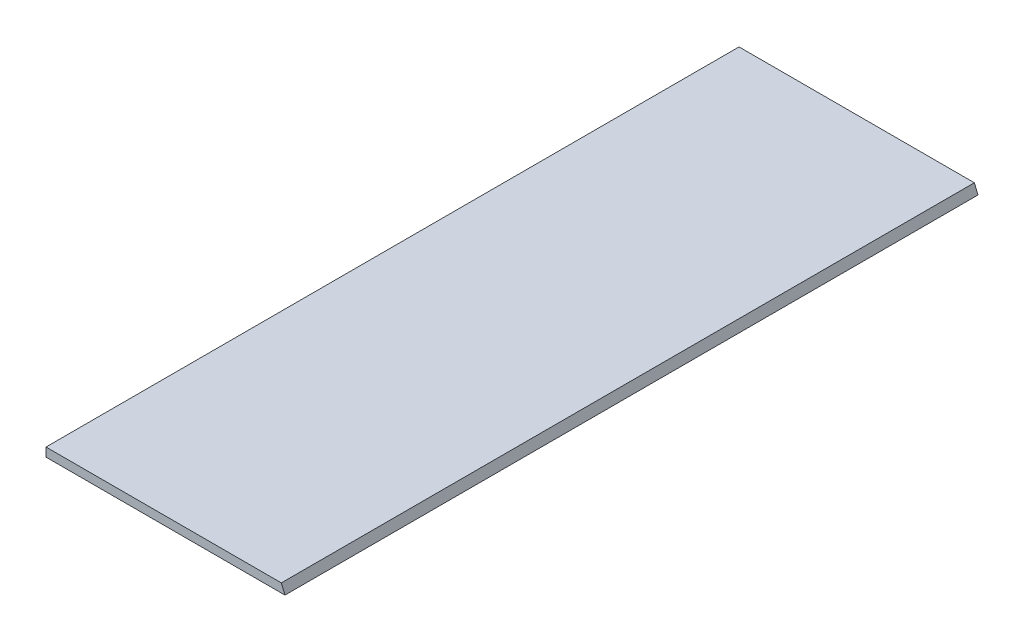
SolidWorks part; units mm, degrees
ref_plane "Front Plane" through (0, 0, 0) normal (0, 0, 1) x (1, 0, 0)
ref_plane "Top Plane" through (0, 0, 0) normal (0, 1, 0) x (1, 0, 0)
ref_plane "Right Plane" through (0, 0, 0) normal (1, 0, 0) x (0, 0, -1)
sketch "Sketch1" plane through (0, 0, 0) normal (0, 0, 1) x (1, 0, 0)
  line L0 (0, 0) -> (0, 6.35)
  line L1 (0, 6.35) -> (170.3437, 6.35)
  line L2 (170.3437, 6.35) -> (172.974, 0)
  line L3 (172.974, 0) -> (0, 0)
  dimension "D1" = 6.35
  dimension "D2" = 172.974
  dimension "D3" = 67.5
extrude "Boss-Extrude1" add sketch "Sketch1" along normal blind 501.65
